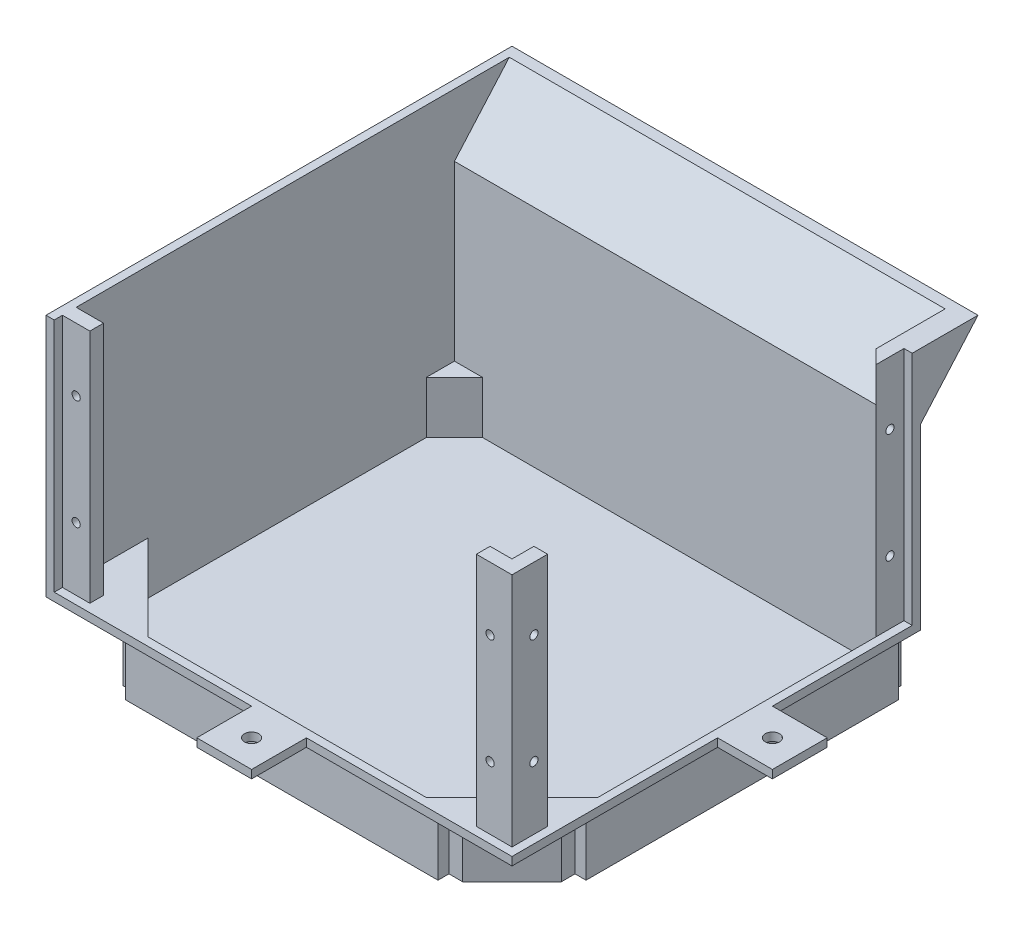
SolidWorks part; units mm, degrees
ref_plane "前视基准面" through (0, 0, 0) normal (0, 0, 1) x (1, 0, 0)
ref_plane "上视基准面" through (0, 0, 0) normal (0, 1, 0) x (1, 0, 0)
ref_plane "右视基准面" through (0, 0, 0) normal (1, 0, 0) x (0, 0, -1)
other "Configuration Table"
sketch "草图1" plane through (0, 0, 0) normal (0, 1, 0) x (1, 0, 0)
  line L21 (-80, 62) -> (-62, 80)
  line L23 (-85, 57) -> (-85, -57)
  line L26 (-85, 57) -> (-80, 57)
  line L27 (-80, 57) -> (-80, 62)
  line L28 (-57, 85) -> (-57, 80)
  line L30 (85, 57) -> (80, 57)
  line L31 (80, 57) -> (80, 62)
  line L33 (85, -57) -> (80, -57)
  line L34 (80, -57) -> (80, -62)
  line L37 (-85, -57) -> (-80, -57)
  line L38 (-80, -57) -> (-80, -62)
  line L39 (-57, 80) -> (-62, 80)
  line L40 (-57, 85) -> (57, 85)
  line L42 (57, 85) -> (57, 80)
  line L43 (57, 80) -> (62, 80)
  line L44 (62, 80) -> (80, 62)
  line L45 (-57, -85) -> (-57, -80)
  line L46 (-57, -80) -> (-62, -80)
  line L47 (57, -85) -> (57, -80)
  line L48 (57, -80) -> (62, -80)
  line L49 (-80, -62) -> (-62, -80)
  line L50 (85, 57) -> (85, -57)
  line L51 (62, -80) -> (80, -62)
  line L52 (-57, -85) -> (57, -85)
extrude "凸台-拉伸1" add sketch "草图1" along normal blind 4 contours L50 L33 L34 L51 L48 L47 L52 L45 L46 L49 L38 L37 L23 L26 L27 L21 L39 L28 L40 L42 L43 L44 L31 L30
sketch "草图2" plane through (0, 4, 0) normal (0, 1, 0) x (1, 0, 0)
  line L0 (-57, 85) -> (57, 85)
  line L1 (57, 85) -> (57, 80)
  line L2 (57, 80) -> (62, 80)
  line L3 (62, 80) -> (80, 62)
  line L4 (80, 62) -> (80, 57)
  line L5 (80, 57) -> (85, 57)
  line L6 (85, 57) -> (85, -57)
  line L7 (85, -57) -> (80, -57)
  line L8 (80, -57) -> (80, -62)
  line L9 (80, -62) -> (62, -80)
  line L10 (62, -80) -> (57, -80)
  line L11 (57, -80) -> (57, -85)
  line L12 (57, -85) -> (-57, -85)
  line L13 (-57, -85) -> (-57, -80)
  line L14 (-57, -80) -> (-62, -80)
  line L15 (-62, -80) -> (-80, -62)
  line L16 (-80, -62) -> (-80, -57)
  line L17 (-80, -57) -> (-85, -57)
  line L18 (-85, -57) -> (-85, 57)
  line L19 (-85, 57) -> (-80, 57)
  line L20 (-80, 57) -> (-80, 62)
  line L21 (-80, 62) -> (-62, 80)
  line L22 (-62, 80) -> (-57, 80)
  line L23 (-57, 80) -> (-57, 85)
  line L24 (-82, 50.7574) -> (-50.7574, 82)
  line L25 (50.7574, 82) -> (82, 50.7574)
  line L26 (50.7574, -82) -> (82, -50.7574)
  line L28 (-82, 50.7574) -> (-82, -50.7574)
  line L29 (50.7574, 82) -> (-50.7574, 82)
  line L30 (-82, -50.7574) -> (-50.7574, -82)
  line L31 (82, 50.7574) -> (82, -50.7574)
  line L32 (-50.7574, -82) -> (50.7574, -82)
extrude "凸台-拉伸2" add sketch "草图2" along normal blind 16 contours L23 L0 L1 L2 L3 L4 L5 L6 L7 L8 L9 L10 L11 L12 L13 L14 L15 L16 L17 L18 L19 L20 L21 L22 | L26 L31 L25 L29 L24 L28 L30 L32
sketch "草图3" plane through (0, 0, 0) normal (0, -1, 0) x (-1, 0, 0)
  line L0 (57, -85) -> (85, -85)
  line L1 (-57, 85) -> (-85, 85)
  line L3 (85, -85) -> (-85, -85)
  line L4 (85, -85) -> (85, 85)
  line L5 (85, 85) -> (-85, 85)
  line L6 (-85, -85) -> (-85, 85)
extrude "切除-拉伸2" cut sketch "草图3" against normal blind 1 contours L4 L3 L6 L5
sketch "草图4" plane through (0, 20, 0) normal (0, 1, 0) x (1, 0, 0)
  line L0 (-57, 85) -> (-85, 85)
  line L1 (57, -85) -> (85, -85)
  line L3 (-85, 85) -> (85, 85)
  line L4 (-85, 85) -> (-85, -85)
  line L5 (-85, -85) -> (85, -85)
  line L6 (85, 85) -> (85, -85)
  line M31 (82, -50.7574) -> (50.7574, -82)
  line M32 (50.7574, -82) -> (-50.7574, -82)
  line M33 (-50.7574, -82) -> (-82, -50.7574)
  line M34 (-82, -50.7574) -> (-82, 50.7574)
  line M35 (-82, 50.7574) -> (-50.7574, 82)
  line M36 (-50.7574, 82) -> (50.7574, 82)
  line M37 (50.7574, 82) -> (82, 50.7574)
  line M38 (82, 50.7574) -> (82, -50.7574)
extrude "凸台-拉伸3" add sketch "草图4" along normal blind 3 contours M31 M38 M37 M36 M35 M34 M33 M32 | L4 L3 L6 L5 region at (0, 20, 0)
sketch "草图5" plane through (0, 23, 0) normal (0, 1, 0) x (1, 0, 0)
  line L0 (85, 85) -> (85, -85) construction
  line L1 (-85, 85) -> (85, 85)
  line L2 (-85, 85) -> (-85, 82)
  line L3 (-85, 82) -> (85, 82)
  line L4 (85, 85) -> (85, 82)
  line L6 (-85, -85) -> (-82, -85)
  line L7 (-85, -85) -> (-85, 82)
  line L8 (-85, 82) -> (-82, 82)
  line L9 (-82, -85) -> (-82, 82)
  line M13 (-82, -50.7574) -> (-82, 50.7574)
  line M15 (-50.7574, 82) -> (50.7574, 82)
  line M17 (-85, -85) -> (85, -85)
  line M18 (85, -85) -> (85, 85)
  line M19 (85, 85) -> (-85, 85)
  line M20 (-85, 85) -> (-85, -85)
extrude "凸台-拉伸4" add sketch "草图5" along normal blind 86 contours L3 M20 M15 M18 M19 | L9 L3 M17 M13 M20 region at (0, 23, -83.5) region at (-83.5, 23, 1.5)
sketch "草图7" plane through (0, 23, 0) normal (0, 1, 0) x (1, 0, 0)
  line L1 (-82, -85) -> (-82, 82) construction
  line L2 (-82, -82) -> (-82, -79)
  line L3 (-82, -85) -> (-82, -50.7574) construction
  line L8 (50.7574, 82) -> (85, 82) construction
  line L9 (82, 82) -> (79, 82)
  line L13 (-82, -79) -> (-72, -79)
  line L14 (-72, -79) -> (-72, -82)
  line L15 (-82, -82) -> (-72, -82)
  line L16 (82, 82) -> (82, 72)
  line L17 (82, 72) -> (79, 72)
  line L18 (79, 82) -> (79, 72)
  line L19 (50.7574, -82) -> (82, -82)
  line L20 (82, -82) -> (82, -50.7574)
  line L22 (82, -82) -> (79, -82)
  line L23 (82, -82) -> (82, -72)
  line L24 (82, -72) -> (79, -72)
  line L25 (79, -82) -> (79, -72)
  line L26 (82, -82) -> (72, -82)
  line L27 (82, -82) -> (82, -79)
  line L28 (82, -79) -> (72, -79)
  line L29 (72, -82) -> (72, -79)
  line M9 (85, 82) -> (50.7574, 82)
  line M15 (-82, -50.7574) -> (-82, -85)
extrude "凸台-拉伸6" add sketch "草图7" along normal blind 86 contours L15 L14 L13 M15 | L28 L23 L24 L25 | L20 L28 L25 L19 | L29 L19 L25 L28 | L18 L17 L16 M9 region at (-77, 23, 80.5) region at (80.5, 23, -77) region at (75.5, 23, 80.5) region at (80.5, 23, 80.5) region at (80.5, 23, 75.5)
sketch "草图8" plane through (0, 0, 82) normal (0, 0, 1) x (1, 0, 0)
  line L0 (-72, 109) -> (-72, 23)
  line L1 (-72, 66) -> (-77, 66)
  line L2 (-77, 66) -> (-77, 86)
  line L3 (-77, 66) -> (-77, 46)
  line L4 (-77, 86) -> (77, 86)
  line L5 (-77, 46) -> (77, 46)
  circle A0 centre (-77, 86) radius 1.5
  circle A1 centre (-77, 46) radius 1.5
extrude "切除-拉伸3" cut sketch "草图8" against normal blind 86 contours L4 A0 L2 | L2 A0 L4 | L5 A1 L3 | L3 A1 L5 region at (-76.3634, 85.3634, 82) region at (-77.2122, 86.2122, 82) region at (-77.2122, 45.7878, 82) region at (-76.3634, 46.6366, 82)
sketch "草图9" plane through (82, 0, 0) normal (1, 0, 0) x (0, 0, -1)
  line L0 (72, 109) -> (72, 23)
  line L1 (72, 66) -> (82, 66)
  line L2 (82, 109) -> (82, 23) construction
  line L3 (77, 66) -> (77, 86)
  line L4 (77, 66) -> (77, 46)
  line L5 (77, 46) -> (-77, 46)
  line L8 (77, 86) -> (-77, 86)
  circle A0 centre (77, 86) radius 1.6062
  circle A1 centre (77, 46) radius 2.0555
extrude "切除-拉伸4" cut sketch "草图9" against normal blind 86 contours L3 A0 L8 | L8 A0 L3 | L5 A1 L4 | L4 A1 L5 region at (82, 86.2272, -77.2272) region at (82, 85.3183, -76.3183) region at (82, 46.8724, -76.1276) region at (82, 45.7092, -77.2908)
sketch "草图10" plane through (0, 109, 0) normal (0, 1, 0) x (1, 0, 0)
  line L1 (79, -72) -> (82, -72)
  line L2 (79, -72) -> (79, -69)
  line L3 (79, -69) -> (82, -69)
  line L4 (82, -72) -> (82, -69)
  line L5 (72, -82) -> (69, -82)
  line L6 (72, -82) -> (72, -79)
  line L7 (72, -79) -> (69, -79)
  line L8 (69, -82) -> (69, -79)
extrude "凸台-拉伸7" add sketch "草图10" against normal blind 86
sketch "草图11" plane through (0, 0, 82) normal (0, 0, 1) x (1, 0, 0)
  line L0 (-77, 86) -> (69, 86)
  line L1 (69, 23) -> (69, 109) construction
  line L2 (69, 86) -> (74, 86)
  line L3 (74, 86) -> (74, 46)
  circle A2 centre (74, 86) radius 1.5
  circle A3 centre (74, 46) radius 1.5
extrude "切除-拉伸5" cut sketch "草图11" against normal blind 86 contours L3 A2 L2 | L2 A2 L3 | A3 region at (74.2122, 86.2122, 82) region at (75.0307, 47.0307, 82) region at (73.3634, 85.3634, 82)
sketch "草图12" plane through (0, 109, 0) normal (0, 1, 0) x (1, 0, 0)
  line L0 (79, -79) -> (79, -69) construction
  line L1 (69, -79) -> (79, -79)
  line L2 (69, -79) -> (69, -77)
  line L3 (69, -77) -> (79, -77)
  line L4 (79, -79) -> (79, -77)
  line L6 (79, -69) -> (77, -69)
  line L7 (79, -69) -> (79, -77)
  line L8 (79, -77) -> (77, -77)
  line L9 (77, -69) -> (77, -77)
  line M9 (79, -69) -> (79, -79)
  line M10 (79, -79) -> (69, -79)
extrude "凸台-拉伸8" add sketch "草图12" against normal blind 86 contours L6 L9 L3 M9 | L3 L2 M10 M9 region at (74, 109, 78) region at (78, 109, 73)
sketch "草图13" plane through (0, 0, 82) normal (0, 0, 1) x (1, 0, 0)
  circle A0 centre (74, 86) radius 1.5
  circle A1 centre (74, 46) radius 1.5
extrude "切除-拉伸6" cut sketch "草图13" against normal blind 86
sketch "草图14" plane through (0, 0, 77) normal (0, 0, -1) x (-1, 0, 0)
  circle A0 centre (-74, 86) radius 3
  circle A1 centre (-74, 46) radius 3
extrude "切除-拉伸7" cut sketch "草图14" against normal blind 2
sketch "草图15" plane through (82, 0, 0) normal (1, 0, 0) x (0, 0, -1)
  line L0 (77, 86) -> (-69, 86)
  line L1 (-69, 23) -> (-69, 109) construction
  line L2 (-69, 86) -> (-74, 86)
  line L3 (-74, 86) -> (-74, 46)
  circle A0 centre (-74, 86) radius 1.5
  circle A1 centre (-74, 46) radius 1.5
extrude "切除-拉伸8" cut sketch "草图15" against normal blind 5 contours L2 A0 L3 | L3 A0 L2 | A1 region at (82, 85.3634, 73.3634) region at (82, 86.2122, 74.2122) region at (82, 47.0307, 72.9693)
sketch "草图16" plane through (77, 0, 0) normal (-1, 0, 0) x (0, 0, 1)
  circle A0 centre (74, 86) radius 3
  circle A1 centre (74, 46) radius 3
extrude "切除-拉伸9" cut sketch "草图16" against normal blind 2
sketch "草图17" plane through (0, 109, 0) normal (0, 1, 0) x (1, 0, 0)
  line L0 (-82, -79) -> (-82, -50.7574) construction
  line L1 (-72, -79) -> (-82, -79)
  line L2 (-72, -79) -> (-72, -77)
  line L3 (-72, -77) -> (-82, -77)
  line L4 (-82, -79) -> (-82, -77)
  line L5 (50.7574, 82) -> (79, 82) construction
  line L6 (79, 72) -> (77, 72)
  line L7 (79, 72) -> (79, 82)
  line L8 (79, 82) -> (77, 82)
  line L9 (77, 72) -> (77, 82)
extrude "凸台-拉伸9" add sketch "草图17" against normal blind 86
sketch "草图18" plane through (77, 0, 0) normal (-1, 0, 0) x (0, 0, 1)
  line L0 (-72, 66) -> (-77, 66)
  line L1 (-72, 23) -> (-72, 109) construction
  line L2 (-77, 66) -> (-77, 86)
  line L3 (-77, 66) -> (-77, 46)
  circle A0 centre (-77, 86) radius 3
  circle A1 centre (-77, 46) radius 3
extrude "切除-拉伸10" cut sketch "草图18" against normal blind 2 contours A0 | A1 region at (77, 88.0613, -79.0613) region at (77, 48.0613, -74.9387)
sketch "草图19" plane through (0, 0, 77) normal (0, 0, -1) x (-1, 0, 0)
  line L0 (72, 66) -> (82, 66)
  line L1 (72, 23) -> (72, 109) construction
  line L2 (82, 23) -> (82, 109) construction
  line L3 (77, 66) -> (77, 86)
  line L4 (77, 66) -> (77, 46)
  circle A0 centre (77, 86) radius 3
  circle A1 centre (77, 46) radius 3
extrude "切除-拉伸11" cut sketch "草图19" against normal blind 2 contours A0 | A1 region at (-74.9387, 88.0613, 77) region at (-79.0613, 48.0613, 77)
sketch "草图22" plane through (0, 23, 0) normal (0, 1, 0) x (1, 0, 0)
  line L0 (0, 0) -> (85, 0)
  line L2 (85, 82) -> (85, -85) construction
  line L3 (0, 0) -> (-85, 0)
  line L4 (105, 0) -> (105, 10)
  line L9 (85, 0) -> (85, -10)
  line L10 (0, 0) -> (0, -85)
  line L11 (85, -10) -> (105, -10)
  line L12 (85, -10) -> (85, 10)
  line L13 (85, 10) -> (105, 10)
  line L14 (105, -10) -> (105, 10)
  line L15 (-82, -85) -> (85, -85) construction
  line L16 (-85, 85) -> (-85, -85) construction
  line L17 (0, -105) -> (10, -105)
  line L18 (0, -85) -> (-10, -85)
  line L19 (-85, 0) -> (-105, 0)
  line L20 (-10, -85) -> (10, -85)
  line L21 (-10, -85) -> (-10, -105)
  line L22 (-10, -105) -> (10, -105)
  line L23 (10, -85) -> (10, -105)
  line L24 (-105, 0) -> (-105, 20)
  line L25 (-105, 20) -> (-85, 20)
  line L26 (-85, 20) -> (-85, 0)
  circle A1 centre (0, -95) radius 2.6
  circle A2 centre (95, 0) radius 2.6
  circle A3 centre (-95, 10) radius 2.6
  line M47 (-82, -85) -> (85, -85)
  line M48 (85, -85) -> (85, 82)
extrude "凸台-拉伸10" add sketch "草图22" against normal blind 3 contours L26 L25 L24 L19 A3 | L23 L21 L22 L17 A1 M47 | L11 L14 L4 L13 A2 M48 region at (-95, 23, -0.2828) region at (85.2828, 23, -5) region at (5, 23, 85.2828)
sketch "草图23" plane through (0, 109, 0) normal (0, 1, 0) x (1, 0, 0)
  line L0 (-85, 85) -> (-85, 65)
  line L1 (-85, 85) -> (-85, -85) construction
  line L2 (-85, 65) -> (85, 65)
  line L3 (85, 82) -> (85, 10) construction
  line L4 (85, 65) -> (85, 85)
  line L5 (85, 85) -> (-85, 85)
extrude "切除-拉伸12" cut sketch "草图23" against normal blind 100 contours L5 L0 L2 L4
sketch "草图25" plane through (0, 4, 0) normal (0, 1, 0) x (1, 0, 0)
  line L0 (85, 65) -> (85, 10) construction
  line L1 (-82, 65) -> (85, 65)
  line L2 (-82, 65) -> (-82, 62)
  line L3 (-82, 62) -> (85, 62)
  line L4 (85, 65) -> (85, 62)
extrude "凸台-拉伸11" add sketch "草图25" along normal blind 105
sketch "草图26" plane through (0, 1, 0) normal (0, -1, 0) x (1, 0, 0)
  line L0 (80, -65) -> (77, -65)
  line L1 (80, -62) -> (85, -62)
  line L3 (80, -65) -> (85, -65)
  line L4 (85, -62) -> (85, -65)
  line L5 (77, -65) -> (80, -62)
  line L6 (-77, -65) -> (-82, -65) construction
  line L7 (-82, -62) -> (-80, -62)
  line L8 (-82, -62) -> (-82, -65)
  line L9 (-82, -65) -> (-80, -65)
  line L11 (-80, -62) -> (-77, -65)
  line L12 (-80, -62) -> (-62, -80) construction
  line L13 (-80, -62) -> (-77, -65) construction
  line L14 (-77, -65) -> (-80, -65)
extrude "切除-拉伸14" cut sketch "草图26" against normal blind 19
sketch "草图28" plane through (0, 1, 0) normal (0, -1, 0) x (1, 0, 0)
  line L0 (57, 85) -> (57, 80) construction
  line L1 (-57, 85) -> (57, 85)
  line L2 (-57, 85) -> (-57, 84)
  line L3 (-57, 84) -> (57, 84)
  line L4 (57, 85) -> (57, 84)
  line L5 (85, -57) -> (80, -57) construction
  line L6 (85, 57) -> (84, 57)
  line L7 (85, 57) -> (85, -57)
  line L8 (85, -57) -> (84, -57)
  line L9 (84, 57) -> (84, -57)
  line L10 (57, -85) -> (57, -80) construction
  line L11 (-57, -85) -> (57, -85)
  line L12 (-57, -85) -> (-57, -84)
  line L13 (-57, -84) -> (57, -84)
  line L14 (57, -85) -> (57, -84)
  line L15 (-85, -57) -> (-80, -57) construction
  line L16 (-85, 57) -> (-84, 57)
  line L17 (-85, 57) -> (-85, -57)
  line L18 (-85, -57) -> (-84, -57)
  line L19 (-84, 57) -> (-84, -57)
extrude "切除-拉伸15" cut sketch "草图28" against normal blind 19
sketch "草图29" plane through (0, 109, 0) normal (0, 1, 0) x (1, 0, 0)
  line L0 (82, 50.7574) -> (82, 62)
  line L1 (-82, 62) -> (85, 62) construction
  line L2 (82, 62) -> (79, 62)
  line L4 (70.7574, 62) -> (82, 50.7574) construction
  line L5 (79, 53.7574) -> (82, 50.7574)
  line L6 (79, 62) -> (77, 62)
  line L7 (77, 62) -> (77, 55.7574)
  line L8 (77, 55.7574) -> (79, 53.7574)
extrude "凸台-拉伸12" add sketch "草图29" against normal blind 90 contours L2 L6 L7 L8 L5 L0
sketch "草图32" plane through (0, 109, 0) normal (0, 1, 0) x (1, 0, 0)
  line L0 (85, 62) -> (85, 65) construction
  line L1 (-85, 65) -> (85, 65)
  line L2 (-85, 65) -> (-85, 64)
  line L3 (-85, 64) -> (85, 64)
  line L4 (85, 65) -> (85, 64)
extrude "切除-拉伸18" cut sketch "草图32" against normal blind 100
sketch "草图33" plane through (0, 9, 0) normal (0, 1, 0) x (1, 0, 0)
  line L0 (67.7574, 65) -> (-67.7574, 65)
  line L1 (-67.7574, 65) -> (-68.7574, 64)
  line L2 (-85, 64) -> (85, 64) construction
  line L3 (-68.7574, 64) -> (67.7574, 64)
  line L4 (67.7574, 65) -> (68.7574, 64)
  line L5 (68.7574, 64) -> (67.7574, 64)
extrude "切除-拉伸19" cut sketch "草图33" against normal blind 5 contours L5 L3 L1 L0 L4
sketch "草图34" plane through (0, 109, 0) normal (0, 1, 0) x (1, 0, 0)
  line L0 (-82, -77) -> (-82, 62) construction
  line L1 (77, 62) -> (-82, 62)
  line L2 (77, 62) -> (77, 61)
  line L3 (77, 61) -> (-82, 61)
  line L4 (-82, 62) -> (-82, 61)
  line L5 (82, 50.7574) -> (82, 62) construction
  line L6 (85, 62) -> (82, 62)
  line L7 (85, 62) -> (85, 61)
  line L8 (85, 61) -> (82, 61)
  line L9 (82, 62) -> (82, 61)
extrude "凸台-拉伸13" add sketch "草图34" against normal blind 105 contours L2 L1 L4 L3 | L7 L6 L9 L8
sketch "草图35" plane through (0, 4, 0) normal (0, -1, 0) x (-1, 0, 0)
  line L1 (-80, 57) -> (-85, 57)
  line L2 (-80, 57) -> (-80, 62)
  line L3 (-80, 62) -> (-85, 62)
  line L4 (-85, 57) -> (-85, 62)
extrude "切除-拉伸20" cut sketch "草图35" against normal blind 16 contours L2 L1 L4 L3
sketch "草图36" plane through (0, 4, 0) normal (0, -1, 0) x (1, 0, 0)
  line L1 (-82, -61) -> (-80, -61)
  line L2 (-82, -61) -> (-82, -62)
  line L3 (-82, -62) -> (-80, -62)
  line L4 (-80, -61) -> (-80, -62)
extrude "切除-拉伸21" cut sketch "草图36" against normal blind 16
sketch "草图37" plane through (82, 0, 0) normal (1, 0, 0) x (0, 0, -1)
  line L4 (55.8787, 86) -> (55.8787, 46)
  circle A0 centre (55.8787, 86) radius 1.5
  circle A1 centre (55.8787, 46) radius 1.5
extrude "切除-拉伸22" cut sketch "草图37" against normal blind 16 contours A0 | A1 region at (82, 47.0307, -56.9093) region at (82, 87.0307, -54.848)
sketch "草图38" plane through (77, 0, 0) normal (-1, 0, 0) x (0, 0, 1)
  circle A0 centre (-55.8787, 86) radius 3
  circle A1 centre (-55.8787, 46) radius 3
extrude "切除-拉伸23" cut sketch "草图38" against normal blind 2
sketch "草图39" plane through (85, 0, 0) normal (1, 0, 0) x (0, 0, -1)
  line L4 (64, 109) -> (85, 109)
  line L8 (64, 85) -> (85, 109)
  line L9 (64, 109) -> (64, 85)
extrude "凸台-拉伸14" add sketch "草图39" against normal blind 170
sketch "草图40" plane through (85, 0, 0) normal (1, 0, 0) x (0, 0, -1)
  line L1 (61, 23) -> (61, 109) construction
  line L6 (61, 109) -> (81.0137, 109)
  line L7 (61, 109) -> (85, 109) construction
  line L8 (81.0137, 109) -> (61, 86.1272)
  line L9 (61, 109) -> (61, 86.1272)
extrude "切除-拉伸24" cut sketch "草图40" against normal blind 167 contours L8 L6 L9
sketch "草图41" plane through (85, 0, 0) normal (1, 0, 0) x (0, 0, -1)
  line L0 (61, 86.1272) -> (61, 109)
  line L1 (61, 109) -> (81.0137, 109)
  line L2 (81.0137, 109) -> (61, 86.1272)
extrude "凸台-拉伸15" add sketch "草图41" against normal blind 8
